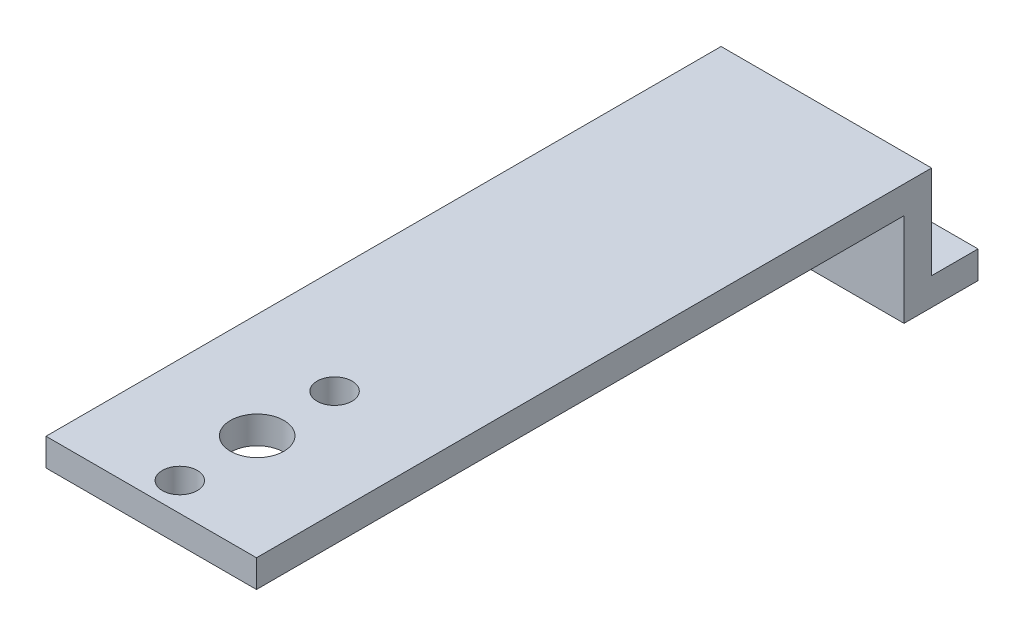
SolidWorks part; units mm, degrees
ref_plane "Front Plane" through (0, 0, 0) normal (0, 0, 1) x (1, 0, 0)
ref_plane "Top Plane" through (0, 0, 0) normal (0, 1, 0) x (1, 0, 0)
ref_plane "Right Plane" through (0, 0, 0) normal (1, 0, 0) x (0, 0, -1)
sketch "Sketch1" plane through (0, 0, 0) normal (1, 0, 0) x (0, 0, -1)
  line L1 (0.889, 3.903) -> (-0.889, 3.903)
  line L2 (0.889, 3.903) -> (0.889, -2.125)
  line L4 (-0.889, 2.125) -> (-0.889, -3.903)
  line L7 (-0.889, 3.903) -> (-42.731, 3.903)
  line L9 (-0.889, 2.125) -> (-42.731, 2.125)
  line L10 (-42.731, 3.903) -> (-42.731, 2.125)
  line L11 (-0.889, -3.903) -> (3.889, -3.903)
  line L13 (0.889, -2.125) -> (3.889, -2.125)
  line L14 (3.889, -3.903) -> (3.889, -2.125)
  point P0 (0, 0)
  dimension "D1" = 1.778
  dimension "D2" = 1.778
  dimension "D3" = 1.778
  dimension "D4" = 4.25
  dimension "D5" = 43.62
  dimension "D6" = 3
extrude "Boss-Extrude1" add sketch "Sketch1" along normal blind 6.8 and the other way blind 6.8
sketch "Sketch2" plane through (0, 3.903, 0) normal (0, 1, 0) x (1, 0, 0)
  circle A0 centre (0, -40.8857) radius 1.1303 construction
  circle A1 centre (0, -35.8857) radius 1.7272 construction
  circle A2 centre (0, -30.8857) radius 1.1303 construction
  circle A3 centre (0, -40.8857) radius 1.1303
  circle A4 centre (0, -35.8857) radius 1.7272
  circle A5 centre (0, -30.8857) radius 1.1303
extrude "Cut-Extrude1" cut sketch "Sketch2" against normal up to next
